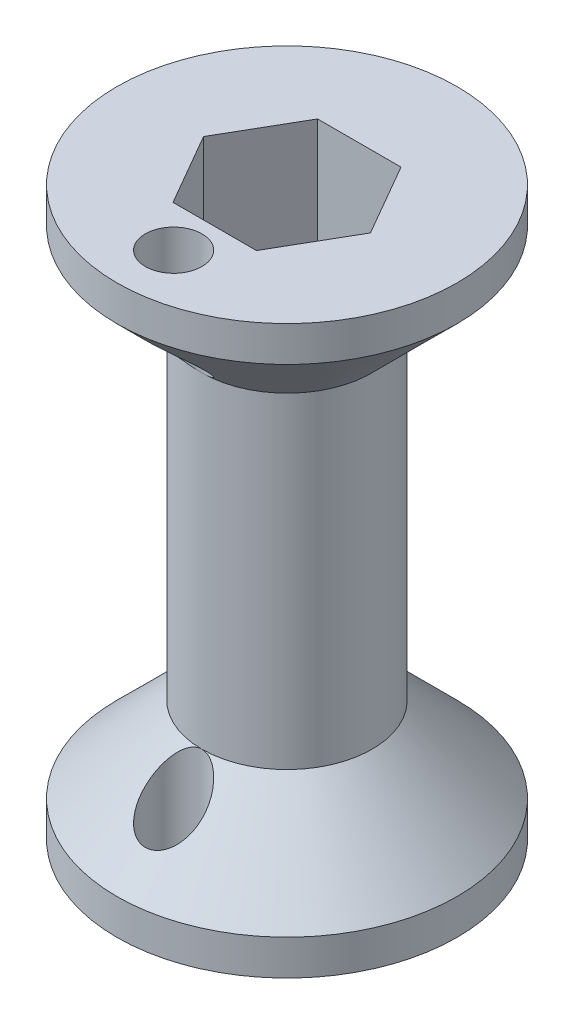
SolidWorks part; units mm, degrees
ref_plane "Front Plane" through (0, 0, 0) normal (0, 0, 1) x (1, 0, 0)
ref_plane "Top Plane" through (0, 0, 0) normal (0, 1, 0) x (1, 0, 0)
ref_plane "Right Plane" through (0, 0, 0) normal (1, 0, 0) x (0, 0, -1)
sketch "Sketch1" plane through (0, 0, 0) normal (1, 0, 0) x (0, 0, -1)
  line L0 (0, 0) -> (0, 25.4)
  line L1 (0, 25.4) -> (15.24, 25.4)
  line L2 (15.24, 25.4) -> (15.24, 22.225)
  line L3 (15.24, 22.225) -> (7.62, 14.605)
  line L4 (7.62, 14.605) -> (7.62, 0)
  line L5 (7.62, 0) -> (0, 0)
  dimension "D1" = 25.4
  dimension "D2" = 45
  dimension "D3" = 3.175
  dimension "D4" = 7.62
  dimension "D5" = 15.24
  dimension "D6" = 14.605
revolve "Revolve1" add sketch "Sketch1" angle 360 about L0
mirror "Mirror1" about plane through (0, 0, -7.62) normal (0, -1, 0) of "Revolve1"
sketch "Sketch2" plane through (0, 25.4, 0) normal (0, 1, 0) x (1, 0, 0)
  line L1 (-7.479, 0) -> (-3.7395, -6.477)
  line L2 (-3.7395, -6.477) -> (3.7395, -6.477)
  line L3 (3.7395, -6.477) -> (7.479, 0)
  line L4 (7.479, 0) -> (3.7395, 6.477)
  line L5 (3.7395, 6.477) -> (-3.7395, 6.477)
  line L6 (-3.7395, 6.477) -> (-7.479, 0)
  circle A0 centre (0, 0) radius 6.477 construction
  circle A1 centre (0, -10.16) radius 2.54
  circle A2 centre (0, 0) radius 15.24 construction
  dimension "D2" = 5.08
  dimension "D1" = 12.954
  dimension "." = 10.16
extrude "Cut-Extrude1" cut sketch "Sketch2" against normal through all
